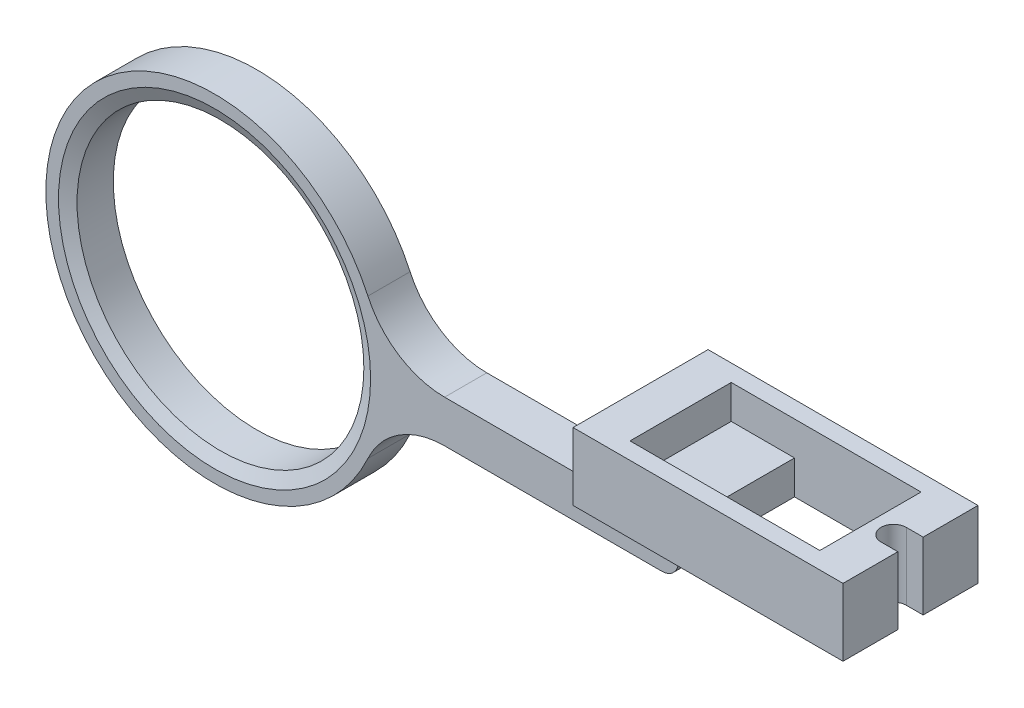
SolidWorks part; units mm, degrees
ref_plane "Plan de face" through (0, 0, 0) normal (0, 0, 1) x (1, 0, 0)
ref_plane "Plan de dessus" through (0, 0, 0) normal (0, 1, 0) x (1, 0, 0)
ref_plane "Plan de droite" through (0, 0, 0) normal (1, 0, 0) x (0, 0, -1)
sketch "Sketch1" plane through (0, 0, 0) normal (0, 0, 1) x (1, 0, 0)
  line L1 (0, 2.5) -> (80, 2.5)
  line L2 (0, 2.5) -> (0, -2.5)
  line L3 (0, -2.5) -> (80, -2.5)
  line L4 (80, 2.5) -> (80, -2.5)
  circle A0 centre (0, 0) radius 20
  circle A1 centre (0, 0) radius 17
  point P9 (0, 0)
  dimension "D1" = 40
  dimension "D3" = 80
  dimension "D4" = 5
  dimension "D2" = 3
extrude "Boss-Extrude1" add sketch "Sketch1" along normal blind 5 contours A1 L1 A0 L3 | A1 L3 A0 L1 | A0 L3 L4 L1 region at (-17.5646, 0, 0) region at (18.443, 0, 0) region at (49.9739, 0, 0)
chamfer "Chamfer2" distance 1.5 angle 25 1 edges at (17, 0, 5) first distance on face at (39.9608, 0, 5)
fillet "Fillet1" radius 10 2 edges at (19.8431, -2.5, 2.5) (19.8431, 2.5, 2.5)
sketch "Sketch4" plane through (0, 0, 0) normal (0, 1, 0) x (1, 0, 0)
  line L0 (18.5, -5) -> (17, -4.3005) construction
  circle A0 centre (0.2012, -29.5685) radius 30 construction
  dimension "D1" = 60
sketch "Sketch10" plane through (0, 2.5, 0) normal (0, 1, 0) x (1, 0, 0)
  line L0 (27.2718, 0) -> (80, 0) construction
  line L1 (80, -5) -> (48, -5)
  line L2 (80, -5) -> (80, 0)
  line L3 (80, 0) -> (48, 0)
  line L4 (48, -5) -> (48, 0)
  dimension "D1" = 32
extrude "Boss-Extrude3" add sketch "Sketch10" along normal blind 2
sketch "Sketch5" plane through (0, 4.5, 0) normal (0, 1, 0) x (1, 0, 0)
  line L0 (80, -5) -> (80, 0) construction
  line L1 (80, -10.5) -> (48, -10.5)
  line L2 (80, -10.5) -> (80, 5.5)
  line L3 (80, 5.5) -> (48, 5.5)
  line L4 (48, -10.5) -> (48, 5.5)
  point P7 (80, -2.5)
  point P8 (80, -2.5)
  dimension "D1" = 16
  dimension "D2" = 32
extrude "Boss-Extrude2" add sketch "Sketch5" along normal blind 8
sketch "Sketch6" plane through (0, 12.5, 0) normal (0, 1, 0) x (1, 0, 0)
  line L0 (80, 5.5) -> (48, 5.5) construction
  line L1 (52.75, 3.5) -> (75.25, 3.5)
  line L2 (52.75, 3.5) -> (52.75, -8.5)
  line L3 (52.75, -8.5) -> (75.25, -8.5)
  line L4 (75.25, 3.5) -> (75.25, -8.5)
  line L5 (80, -10.5) -> (80, 5.5) construction
  point P6 (64, 5.5)
  point P7 (64, 3.5)
  point P10 (80, -2.5)
  point P11 (75.25, -2.5)
  dimension "D1" = 12
  dimension "D2" = 22.5
extrude "Cut-Extrude1" cut sketch "Sketch6" against normal blind 4
sketch "Sketch7" plane through (0, -2.5, 0) normal (0, -1, 0) x (1, 0, 0)
  line L0 (27.2718, 0) -> (80, 0) construction
  line L1 (80, 5) -> (55, 5)
  line L2 (80, 5) -> (80, 0)
  line L3 (80, 0) -> (55, 0)
  line L4 (55, 5) -> (55, 0)
  dimension "D1" = 25
extrude "Cut-Extrude2" cut sketch "Sketch7" against normal up to surface (7 mm away) up to face at (64, 4.5, -2.75)
sketch "Sketch8" plane through (0, 8.5, 0) normal (0, 1, 0) x (1, 0, 0)
  line L0 (52.75, -8.5) -> (75.25, -8.5) construction
  line L1 (75.25, 3.5) -> (60.25, 3.5)
  line L2 (75.25, 3.5) -> (75.25, -8.5)
  line L3 (75.25, -8.5) -> (60.25, -8.5)
  line L4 (60.25, 3.5) -> (60.25, -8.5)
  dimension "D1" = 15
extrude "Cut-Extrude3" cut sketch "Sketch8" against normal through all
sketch "Sketch9" plane through (0, 4.5, 0) normal (0, -1, 0) x (1, 0, 0)
  line L0 (80, 10.5) -> (80, -5.5) construction
  line L3 (78, 4) -> (80, 4)
  line L4 (80, 4) -> (80, 1)
  line L5 (80, 1) -> (78, 1)
  arc A0 (78, 4) -> (78, 1) centre (78, 2.5) ccw
  point P6 (80, 2.5)
  dimension "D1" = 3
  dimension "D2" = 2
extrude "Cut-Extrude4" cut sketch "Sketch9" against normal through all
fillet "Fillet2" radius 2 3 edges at (55, 4.5, 2.5) (48, 2.5, 2.5) (55, -2.5, 2.5)
fillet "Fillet3" radius 1.5 2 edges at (52.5, 4.5, 5) (52.5, 4.5, 0)
